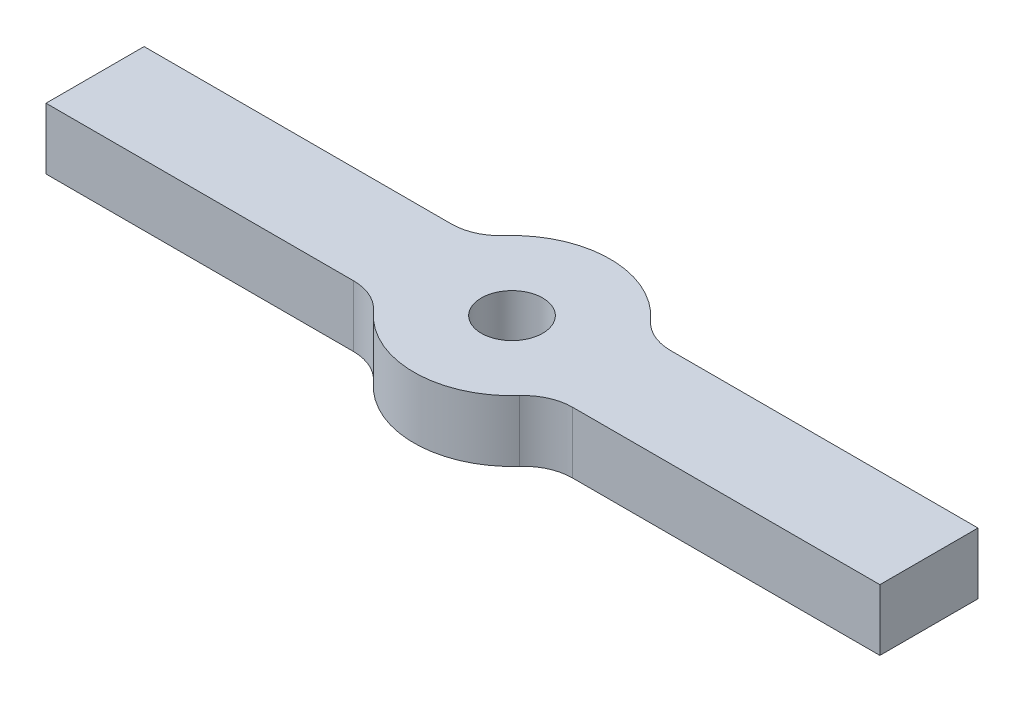
SolidWorks part; units mm, degrees
ref_plane "Front Plane" through (0, 0, 0) normal (0, 0, 1) x (1, 0, 0)
ref_plane "Top Plane" through (0, 0, 0) normal (0, 1, 0) x (1, 0, 0)
ref_plane "Right Plane" through (0, 0, 0) normal (1, 0, 0) x (0, 0, -1)
sketch "Sketch2" plane through (0, 0, 0) normal (0, 1, 0) x (1, 0, 0)
  line L0 (-21.997, 0) -> (0, 0) construction
  line L1 (-107.95, -25.4) -> (-21.997, -25.4)
  line L2 (-107.95, -25.4) -> (-107.95, 0)
  line L3 (-107.95, 0) -> (-21.997, 0)
  line L4 (-21.997, -25.4) -> (-21.997, 0)
  line L5 (21.997, -25.4) -> (107.95, -25.4)
  line L6 (21.997, -25.4) -> (21.997, 0)
  line L7 (21.997, 0) -> (107.95, 0)
  line L8 (107.95, -25.4) -> (107.95, 0)
  line L9 (0, 0) -> (21.997, 0) construction
  circle A0 centre (0, -12.7) radius 7.9375
  circle A1 centre (0, -12.7) radius 25.4
  point P13 (107.95, -12.7)
  dimension "D3" = 215.9
  dimension "D4" = 15.875
  dimension "D5" = 50.8
  dimension "D1" = 25.4
  dimension "D2" = 25.4
extrude "Boss-Extrude1" add sketch "Sketch2" along normal blind 15.875 contours A1 L3 L2 L1 | L4 A1 | L6 A1 L4 A0 | L6 A1 | A1 L5 L8 L7 region at (-66.1179, 0, 12.7) region at (-23.3664, 0, 12.7) region at (-21.325, 0, 12.7) region at (66.1179, 0, 12.7) region at (23.3664, 0, 12.7)
fillet "Fillet1" radius 12.7 4 edges at (21.997, 7.9375, 0) (21.997, 7.9375, 25.4) (-21.997, 7.9375, 25.4) (-21.997, 7.9375, 0)
sketch "Sketch3" plane through (0, 0, 0) normal (0, -1, 0) x (1, 0, 0)
  circle A0 centre (0, 12.7) radius 22.225
  dimension "D1" = 44.45
extrude "Cut-Extrude1" cut sketch "Sketch3" against normal blind 3.175
